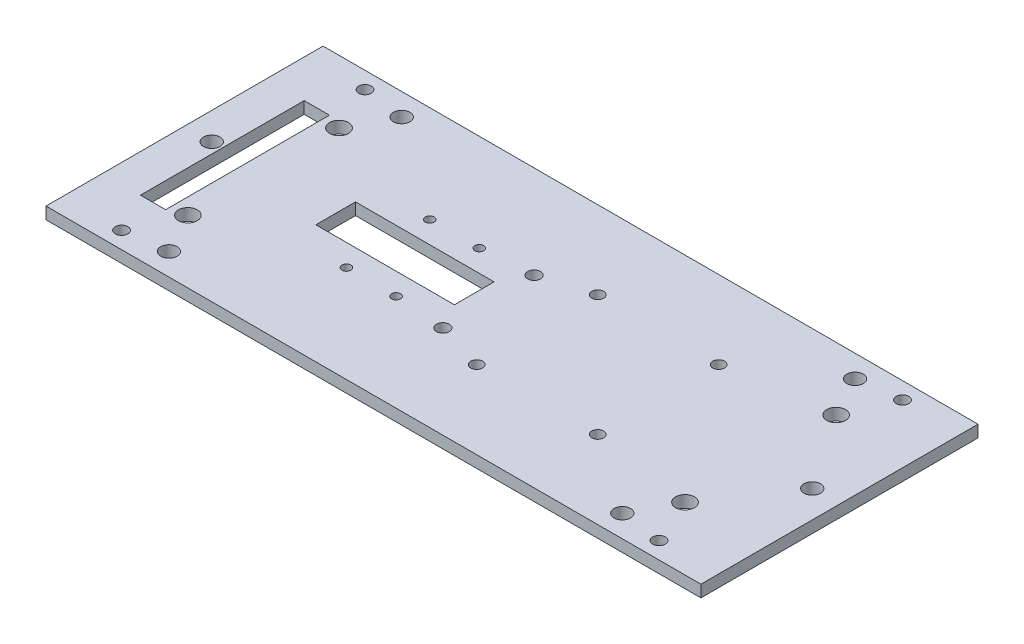
SolidWorks part; units mm, degrees
material "Thornel VCB-20 Carbon Cloth"
ref_plane "Front Plane" through (0, 0, 0) normal (0, 0, 1) x (1, 0, 0)
ref_plane "Top Plane" through (0, 0, 0) normal (0, 1, 0) x (1, 0, 0)
ref_plane "Right Plane" through (0, 0, 0) normal (1, 0, 0) x (0, 0, -1)
sketch "Sketch1" plane through (0, 0, 0) normal (0, 1, 0) x (1, 0, 0)
  line L0 (82.55, -34.925) -> (82.55, 34.925)
  line L1 (82.55, -34.925) -> (-82.55, -34.925)
  line L2 (82.55, 34.925) -> (-82.55, 34.925)
  line L3 (-82.55, -34.925) -> (-82.55, 34.925)
  line L4 (82.55, -34.925) -> (-82.55, 34.925) construction
  line L5 (82.55, 34.925) -> (-82.55, -34.925) construction
  point P1 (0, 0)
  dimension "D1" = 165.1
  dimension "D2" = 69.85
extrude "Boss-Extrude1" add sketch "Sketch1" along normal blind 3
sketch "Sketch6" plane through (0, 0, 0) normal (0, -1, 0) x (1, 0, 0)
  line L0 (-82.55, -34.925) -> (-82.55, 34.925) construction
  line L1 (-44.45, 5) -> (-9.525, 5)
  line L2 (-44.45, 5) -> (-44.45, -5)
  line L3 (-44.45, -5) -> (-9.525, -5)
  line L4 (-9.525, 5) -> (-9.525, -5)
  line L5 (-5.925, -11.501) -> (-63.925, -11.501) construction
  line L6 (-5.925, -11.501) -> (-5.925, 11.501) construction
  line L7 (-5.925, 11.501) -> (-63.925, 11.501) construction
  line L8 (-63.925, -11.501) -> (-63.925, 11.501) construction
  line L9 (-5.925, -11.501) -> (-63.925, 11.501) construction
  line L10 (-5.925, 11.501) -> (-63.925, -11.501) construction
  circle A0 centre (6.35, 15.25) radius 1.5
  circle A1 centre (36.85, 15.25) radius 1.5
  circle A2 centre (6.35, -15.25) radius 1.5
  circle A3 centre (36.85, -15.25) radius 1.5
  circle A4 centre (-63.925, 11.501) radius 1.625 construction
  circle A5 centre (-5.925, 11.501) radius 1.625
  circle A6 centre (-5.925, -11.501) radius 1.625
  circle A7 centre (-63.925, -11.501) radius 1.625 construction
  point P8 (-9.525, 0)
  point P18 (-34.925, 0)
  dimension "D5" = 3
  dimension "D6" = 3
  dimension "D7" = 3
  dimension "D8" = 3
  dimension "D18" = 3.25
  dimension "D1" = 34.925
  dimension "D2" = 10
  dimension "D3" = 38.1
  dimension "D4" = 30.5
  dimension "D9" = 30.5
  dimension "D10" = 30.5
  dimension "D11" = 15.25
  dimension "D12" = 6.35
  dimension "D13" = 15.25
  dimension "D14" = 15.25
  dimension "D15" = 15.25
  dimension "D16" = 23.002
  dimension "D17" = 58
  dimension "D19" = 47.625
  dimension "D20" = 0
extrude "Cut-Extrude1" cut sketch "Sketch6" against normal up to next contours A4 | L4 L1 L2 L3 A4 | A6 | A2 | A3 | A1 | A0 | A7 | A5 region at (-26.9875, 0, 0) region at (6.35, 0, 15.25) region at (36.85, 0, 15.25) region at (6.35, 0, -15.25) region at (36.85, 0, -15.25) region at (-5.925, 0, -11.501)
sketch "Sketch7" plane through (0, 3, 0) normal (0, 1, 0) x (1, 0, 0)
  line L0 (-82.55, 34.925) -> (-82.55, -34.925) construction
  line L1 (82.55, -34.925) -> (82.55, 34.925) construction
  line L2 (-82.55, -34.925) -> (82.55, -34.925) construction
  line L3 (82.55, 34.925) -> (-82.55, 34.925) construction
  circle A0 centre (-77.47, 29.845) radius 1.5
  circle A1 centre (-77.47, -29.845) radius 1.5
  circle A2 centre (77.47, -29.845) radius 1.5
  circle A3 centre (77.47, 29.845) radius 1.5
  dimension "D9" = 3
  dimension "D10" = 3
  dimension "D11" = 3
  dimension "D12" = 3
  dimension "D1" = 5.08
  dimension "D2" = 5.08
  dimension "D3" = 5.08
  dimension "D4" = 5.08
  dimension "D5" = 5.08
  dimension "D6" = 5.08
  dimension "D7" = 5.08
  dimension "D8" = 5.08
sketch "Sketch8" plane through (0, 3, 0) normal (0, 1, 0) x (1, 0, 0)
  line L0 (-82.55, -34.925) -> (82.55, -34.925) construction
  line L1 (-82.55, 34.925) -> (-82.55, -34.925) construction
  line L2 (82.55, -34.925) -> (82.55, 34.925) construction
  line L3 (82.55, 34.925) -> (-82.55, 34.925) construction
  circle A0 centre (-62.6618, -19.05) radius 2.3813
  circle A1 centre (-62.6618, 19.05) radius 2.3813
  circle A2 centre (62.6618, 19.05) radius 2.3813
  circle A3 centre (62.6618, -19.05) radius 2.3813
  dimension "D1" = 4.7625
  dimension "D4" = 4.7625
  dimension "D5" = 4.7625
  dimension "D6" = 4.7625
  dimension "D2" = 15.875
  dimension "D3" = 19.8882
  dimension "D7" = 19.8882
  dimension "D8" = 19.8882
  dimension "D9" = 19.8882
  dimension "D10" = 15.875
  dimension "D11" = 15.875
  dimension "D12" = 15.875
extrude "Cut-Extrude3" cut sketch "Sketch8" against normal up to next
sketch "Sketch9" plane through (0, 3, 0) normal (0, 1, 0) x (1, 0, 0)
  line L0 (-82.55, 34.925) -> (-82.55, -34.925) construction
  line L1 (82.55, -34.925) -> (82.55, 34.925) construction
  circle A0 centre (-75.692, 0) radius 2.0828
  circle A1 centre (75.692, 0) radius 2.0828
  dimension "D1" = 6.858
  dimension "D2" = 6.858
extrude "Cut-Extrude5" cut sketch "Sketch9" against normal blind 5.08
sketch "Sketch10" plane through (0, 3, 0) normal (0, 1, 0) x (1, 0, 0)
  line L0 (-82.55, -34.925) -> (82.55, -34.925) construction
  line L1 (82.55, 34.925) -> (-82.55, 34.925) construction
  circle A0 centre (0, -29.337) radius 2.0828
  circle A1 centre (0, 29.337) radius 2.0828
  circle A2 centre (57.15, -29.337) radius 2.0828
  circle A3 centre (57.15, 29.337) radius 2.0828
  circle A4 centre (-57.15, -29.337) radius 2.0828
  circle A5 centre (-57.15, 29.337) radius 2.0828
  dimension "D1" = 5.588
  dimension "D2" = 5.588
  dimension "D3" = 2
  dimension "D4" = 2
extrude "Cut-Extrude6" cut sketch "Sketch10" against normal blind 5.08 contours A5 | A2 | A3 | A4 region at (57.15, 3, 29.337) region at (57.15, 3, -29.337) region at (-57.15, 3, 29.337) region at (-57.15, 3, -29.337)
sketch "Sketch11" plane through (0, 3, 0) normal (0, 1, 0) x (1, 0, 0)
  line L1 (-18.7375, 10.5) -> (-31.2375, 10.5) construction
  line L2 (-18.7375, 10.5) -> (-18.7375, -10.5) construction
  line L3 (-18.7375, -10.5) -> (-31.2375, -10.5) construction
  line L4 (-31.2375, 10.5) -> (-31.2375, -10.5) construction
  line L5 (-18.7375, 10.5) -> (-31.2375, -10.5) construction
  line L6 (-18.7375, -10.5) -> (-31.2375, 10.5) construction
  line L7 (-9.525, 5) -> (-44.45, 5) construction
  circle A0 centre (-31.2375, 10.5) radius 1.125
  circle A1 centre (-18.7375, 10.5) radius 1.125
  circle A2 centre (-18.7375, -10.5) radius 1.125
  circle A3 centre (-31.2375, -10.5) radius 1.125
  point P0 (-24.9875, 0)
  point P9 (-26.9875, 5)
  dimension "D4" = 2.25
  dimension "D5" = 2.25
  dimension "D6" = 2.25
  dimension "D7" = 2.25
  dimension "D1" = 12.5
  dimension "D2" = 21
  dimension "D3" = 2
extrude "Cut-Extrude7" cut sketch "Sketch11" against normal blind 41.91
sketch "Sketch12" plane through (0, 0, 0) normal (0, -1, 0) x (1, 0, 0)
  line L0 (-24.5963, 23.3735) -> (-5.5463, 23.3735) construction
  line L1 (-24.5963, 24.5641) -> (-5.5463, 24.5641)
  line L2 (-24.5963, 24.5641) -> (-24.5963, 22.1829)
  line L3 (-24.5963, 22.1829) -> (-5.5463, 22.1829)
  line L4 (-5.5463, 24.5641) -> (-5.5463, 22.1829)
  line L5 (-15.0713, 24.5641) -> (-15.0713, 22.1829)
  line L6 (0.8037, 24.5641) -> (0.8037, 22.1829)
  line L7 (0.8037, 24.5641) -> (19.8537, 24.5641)
  line L8 (19.8537, 24.5641) -> (19.8537, 22.1829)
  line L9 (0.8037, 22.1829) -> (19.8537, 22.1829)
  line L10 (26.2037, 24.5641) -> (26.2037, 22.1829)
  line L11 (26.2037, 24.5641) -> (45.2537, 24.5641)
  line L12 (45.2537, 24.5641) -> (45.2537, 22.1829)
  line L13 (26.2037, 22.1829) -> (45.2537, 22.1829)
  line L14 (0.8037, 9.3241) -> (0.8037, 6.9429)
  line L15 (0.8037, 9.3241) -> (19.8537, 9.3241)
  line L16 (19.8537, 9.3241) -> (19.8537, 6.9429)
  line L17 (0.8037, 6.9429) -> (19.8537, 6.9429)
  line L18 (26.2037, 9.3241) -> (26.2037, 6.9429)
  line L19 (26.2037, 9.3241) -> (45.2537, 9.3241)
  line L20 (45.2537, 9.3241) -> (45.2537, 6.9429)
  line L21 (26.2037, 6.9429) -> (45.2537, 6.9429)
  line L22 (-24.5963, 9.3241) -> (-24.5963, 6.9429)
  line L23 (-24.5963, 9.3241) -> (-5.5463, 9.3241)
  line L24 (-5.5463, 9.3241) -> (-5.5463, 6.9429)
  line L25 (-24.5963, 6.9429) -> (-5.5463, 6.9429)
  line L26 (-24.5963, 24.5641) -> (0.8037, 24.5641) construction
  line L27 (-71.2714, 9.2531) -> (-61.3765, 9.2531)
  line L28 (-24.5963, -24.8071) -> (0.8037, -24.8071) construction
  line L29 (-24.5963, -23.6165) -> (-5.5463, -23.6165) construction
  line L30 (-24.5963, -7.1859) -> (-5.5463, -7.1859)
  line L31 (-5.5463, -9.5671) -> (-5.5463, -7.1859)
  line L32 (-24.5963, -9.5671) -> (-5.5463, -9.5671)
  line L33 (-24.5963, -9.5671) -> (-24.5963, -7.1859)
  line L34 (26.2037, -7.1859) -> (45.2537, -7.1859)
  line L35 (45.2537, -9.5671) -> (45.2537, -7.1859)
  line L36 (26.2037, -9.5671) -> (45.2537, -9.5671)
  line L37 (26.2037, -9.5671) -> (26.2037, -7.1859)
  line L38 (0.8037, -7.1859) -> (19.8537, -7.1859)
  line L39 (19.8537, -9.5671) -> (19.8537, -7.1859)
  line L40 (0.8037, -9.5671) -> (19.8537, -9.5671)
  line L41 (0.8037, -9.5671) -> (0.8037, -7.1859)
  line L42 (26.2037, -22.4259) -> (45.2537, -22.4259)
  line L43 (45.2537, -24.8071) -> (45.2537, -22.4259)
  line L44 (26.2037, -24.8071) -> (45.2537, -24.8071)
  line L45 (26.2037, -24.8071) -> (26.2037, -22.4259)
  line L46 (0.8037, -22.4259) -> (19.8537, -22.4259)
  line L47 (19.8537, -24.8071) -> (19.8537, -22.4259)
  line L48 (0.8037, -24.8071) -> (19.8537, -24.8071)
  line L49 (0.8037, -24.8071) -> (0.8037, -22.4259)
  line L50 (-15.0713, -24.8071) -> (-15.0713, -22.4259)
  line L51 (-5.5463, -24.8071) -> (-5.5463, -22.4259)
  line L52 (-24.5963, -22.4259) -> (-5.5463, -22.4259)
  line L53 (-24.5963, -24.8071) -> (-24.5963, -22.4259)
  line L54 (-24.5963, -24.8071) -> (-5.5463, -24.8071)
  line L56 (-3.1651, 10.991) -> (-1.5776, 10.991)
  line L57 (-3.1651, 10.991) -> (-3.1651, 20.516)
  line L58 (-3.1651, 20.516) -> (-1.5776, 20.516)
  line L59 (-1.5776, 10.991) -> (-1.5776, 20.516)
  line L60 (-3.1651, 10.991) -> (-1.5776, 20.516) construction
  line L61 (-3.1651, 20.516) -> (-1.5776, 10.991) construction
  line L66 (-3.1651, -20.759) -> (-1.5776, -20.759)
  line L67 (-1.5776, -11.234) -> (-1.5776, -20.759)
  line L68 (-3.1651, -11.234) -> (-1.5776, -11.234)
  line L69 (-3.1651, -11.234) -> (-3.1651, -20.759)
  line L78 (51.6896, 8.9006) -> (51.6896, 6.5194)
  line L79 (51.6896, 8.9006) -> (70.7396, 8.9006)
  line L80 (70.7396, 8.9006) -> (70.7396, 6.5194)
  line L81 (51.6896, 6.5194) -> (70.7396, 6.5194)
  line L82 (-70.3121, -11.1231) -> (-60.4172, -11.1231)
  line L83 (64.3896, -0.545) -> (-18.1604, -0.545) construction
  line L84 (-70.3121, -11.1231) -> (-70.3121, -9.3903)
  line L85 (51.6896, -7.6094) -> (70.7396, -7.6094)
  line L86 (70.7396, -9.9906) -> (70.7396, -7.6094)
  line L87 (51.6896, -9.9906) -> (70.7396, -9.9906)
  line L88 (51.6896, -9.9906) -> (51.6896, -7.6094)
  line L93 (73.1208, 10.5675) -> (73.1208, 20.0925)
  line L94 (47.7208, 10.5675) -> (49.3083, 10.5675)
  line L95 (47.7208, 10.5675) -> (47.7208, 20.0925)
  line L96 (47.7208, 20.0925) -> (49.3083, 20.0925)
  line L97 (49.3083, 10.5675) -> (49.3083, 20.0925)
  line L98 (47.7208, 10.5675) -> (49.3083, 20.0925) construction
  line L99 (47.7208, 20.0925) -> (49.3083, 10.5675) construction
  line L100 (73.1208, 10.5675) -> (74.7083, 10.5675)
  line L101 (74.7083, 10.5675) -> (74.7083, 20.0925)
  line L102 (73.1208, 20.0925) -> (74.7083, 20.0925)
  line L103 (47.7208, 10.5675) -> (73.1208, 10.5675) construction
  line L104 (47.7208, -21.1825) -> (49.3083, -21.1825)
  line L105 (49.3083, -11.6575) -> (49.3083, -21.1825)
  line L106 (47.7208, -11.6575) -> (49.3083, -11.6575)
  line L107 (47.7208, -11.6575) -> (47.7208, -21.1825)
  line L108 (73.1208, -11.6575) -> (74.7083, -11.6575)
  line L109 (74.7083, -11.6575) -> (74.7083, -21.1825)
  line L110 (73.1208, -21.1825) -> (74.7083, -21.1825)
  line L111 (73.1208, -11.6575) -> (73.1208, -21.1825)
  line L112 (-70.3121, -9.3903) -> (-60.4172, -9.3903)
  line L113 (-60.4172, -11.1231) -> (-60.4172, -9.3903)
  line L114 (-52.8291, -27.8715) -> (-33.7791, -27.8715)
  line L115 (-33.7791, -30.2527) -> (-33.7791, -27.8715)
  line L116 (-52.8291, -30.2527) -> (-33.7791, -30.2527)
  line L117 (-52.8291, -30.2527) -> (-52.8291, -27.8715)
  line L118 (-70.3121, -11.1231) -> (-60.4172, -9.3903) construction
  line L123 (-59.3265, -23.1262) -> (-57.739, -23.1262)
  line L124 (-57.739, -13.6012) -> (-57.739, -23.1262)
  line L125 (-59.3265, -13.6012) -> (-57.739, -13.6012)
  line L126 (-59.3265, -13.6012) -> (-59.3265, -23.1262)
  line L127 (-31.3979, -16.6796) -> (-29.8104, -16.6796)
  line L128 (-29.8104, -16.6796) -> (-29.8104, -26.2046)
  line L129 (-31.3979, -26.2046) -> (-29.8104, -26.2046)
  line L130 (-31.3979, -16.6796) -> (-31.3979, -26.2046)
  line L131 (-70.3121, -9.3903) -> (-60.4172, -11.1231) construction
  line L132 (-71.2714, 9.2531) -> (-71.2714, 10.9859)
  line L133 (-31.3979, 16.4366) -> (-31.3979, 25.9616)
  line L134 (-31.3979, 25.9616) -> (-29.8104, 25.9616)
  line L135 (-29.8104, 16.4366) -> (-29.8104, 25.9616)
  line L136 (-31.3979, 16.4366) -> (-29.8104, 16.4366)
  line L137 (-59.5464, 13.798) -> (-59.5464, 23.323)
  line L138 (-59.5464, 13.798) -> (-57.9589, 13.798)
  line L139 (-57.9589, 13.798) -> (-57.9589, 23.323)
  line L140 (-59.5464, 23.323) -> (-57.9589, 23.323)
  line L145 (-71.2714, 10.9859) -> (-61.3765, 10.9859)
  line L146 (-52.8291, 30.0097) -> (-52.8291, 27.6285)
  line L147 (-52.8291, 30.0097) -> (-33.7791, 30.0097)
  line L148 (-33.7791, 30.0097) -> (-33.7791, 27.6285)
  line L149 (-52.8291, 27.6285) -> (-33.7791, 27.6285)
  line L150 (-61.3765, 9.2531) -> (-61.3765, 10.9859)
  point P8 (-65.3646, -10.2567)
  point P60 (-2.3713, 15.7535)
  point P100 (48.5146, 15.33)
  dimension "D1" = 19.05
  dimension "D2" = 2.3813
  dimension "D3" = 25.4
  dimension "D4" = 15.24
  dimension "D5" = 1.5875
  dimension "D6" = 3.175
  dimension "D7" = 9.525
  dimension "D8" = 7.62
extrude "Cut-Extrude8" [suppressed] cut sketch "Sketch12" against normal blind 21.336 contours L37 L36 L35 L34 | L88 L87 L86 L85 | L45 L44 L43 L42 | L117 L116 L115 L114 | L78 L81 L80 L79 | L10 L13 L12 L11 | L6 L9 L8 L7 | L14 L17 L16 L15 | L107 L104 L105 L106 | L109 L110 L111 L108 | L40 L39 L38 L41 | L48 L47 L46 L49 | L67 L66 L69 L68 | L52 L51 L54 L53 | L30 L31 L32 L33 | L130 L129 L128 L127 | L126 L123 L124 L125 | L93 L102 L101 L100 | L97 L96 L95 L94 | L19 L20 L21 L18 | L56 L59 L58 L57 | L25 L24 L23 L22 | L3 L4 L1 L2 | L135 L134 L133 L136 | L149 L148 L147 L146 | L139 L140 L137 L138 | L27 L150 L145 L132 | L84 L82 L113 L112
sketch "Sketch13" plane through (0, 0, 0) normal (0, -1, 0) x (1, 0, 0)
  line L2 (-82.55, 34.925) -> (82.55, 34.925) construction
  circle A0 centre (-62.6618, 19.05) radius 2.3813 construction
  circle A6 centre (-67.7422, 30.6896) radius 1.5875
  circle A12 centre (67.7422, 30.6896) radius 1.5875
  circle A15 centre (67.7422, -30.6896) radius 1.5875
  circle A16 centre (-67.7422, -30.6896) radius 1.5875
  point P13 (0, 0)
  point P17 (0.9735, -0.4356)
  point P19 (-0.1369, 0.0621)
  dimension "D2" = 3.175
  dimension "D1" = 12.7
  dimension "D3" = 2
  dimension "D4" = 4.2354
extrude "Cut-Extrude9" cut sketch "Sketch13" against normal blind 5
sketch "Sketch15" plane through (0, 0, 0) normal (0, -1, 0) x (1, 0, 0)
  line L0 (-82.55, -34.925) -> (-82.55, 34.925) construction
  line L1 (-73.025, 20.6375) -> (-66.675, 20.6375)
  line L2 (-73.025, 20.6375) -> (-73.025, -20.6375)
  line L3 (-73.025, -20.6375) -> (-66.675, -20.6375)
  line L4 (-66.675, 20.6375) -> (-66.675, -20.6375)
  line L5 (-73.025, 0) -> (-66.675, 0) construction
  dimension "D1" = 6.35
  dimension "D2" = 41.275
  dimension "D3" = 9.525
extrude "Cut-Extrude10" cut sketch "Sketch15" against normal blind 7.62
